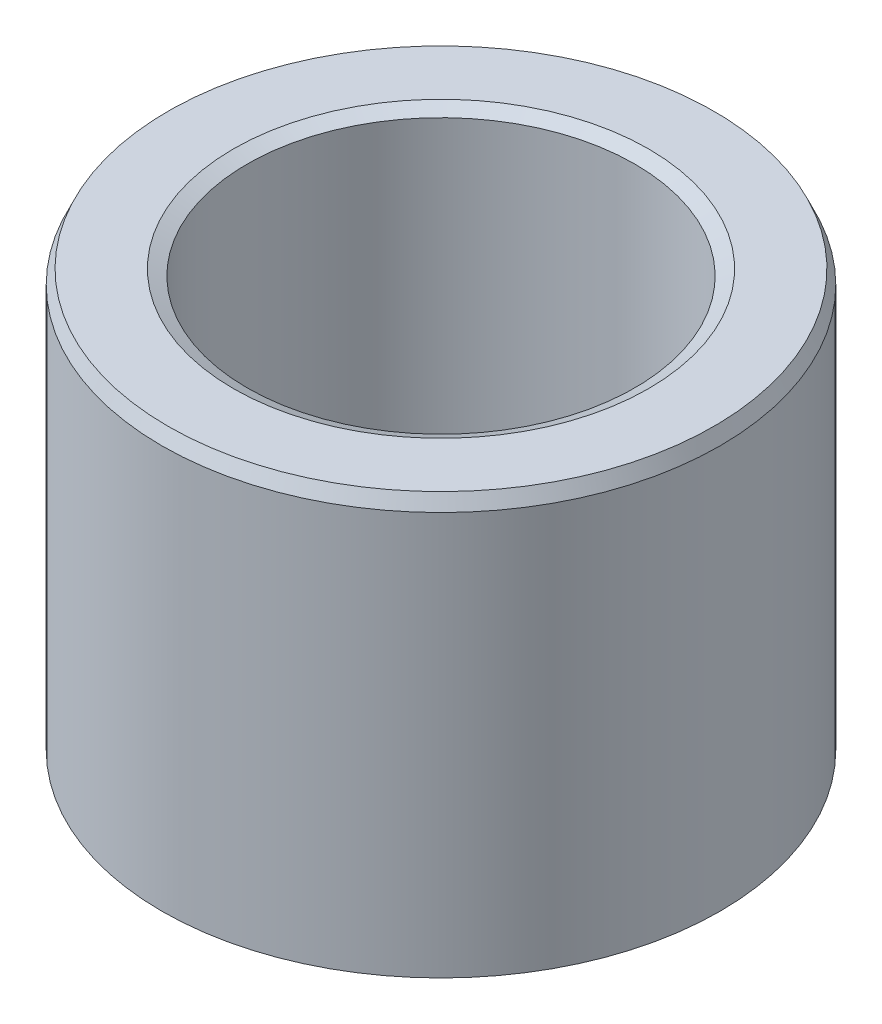
SolidWorks part; units mm, degrees
ref_plane "Front Plane" through (0, 0, 0) normal (0, 0, 1) x (1, 0, 0)
ref_plane "Top Plane" through (0, 0, 0) normal (0, 1, 0) x (1, 0, 0)
ref_plane "Right Plane" through (0, 0, 0) normal (1, 0, 0) x (0, 0, -1)
sketch "Sketch1" plane through (0, 0, 0) normal (0, 1, 0) x (1, 0, 0)
  circle A0 centre (0, 0) radius 10
  dimension "SLEEVE_OD" = 20
extrude "Boss-Extrude1" add sketch "Sketch1" along normal blind 15.1545
sketch "Sketch2" plane through (0, 0, 0) normal (0, 1, 0) x (1, 0, 0)
  circle A0 centre (0, 0) radius 6.9448
  dimension "BORE_D" = 13.8895
extrude "Cut-Extrude1" cut sketch "Sketch2" along normal through all
chamfer "Chamfer1" distance 0.4925 angle 24.359 4 edges at (0, 15.1545, 6.9448) (0, 0, 6.9448) (0, 0, 10) (0, 15.1545, 10) first distance on face at (0, 15.1545, 6.9448) first distance on face at (0, 0, 6.9448) first distance on face at (0, 15.1545, 10)
